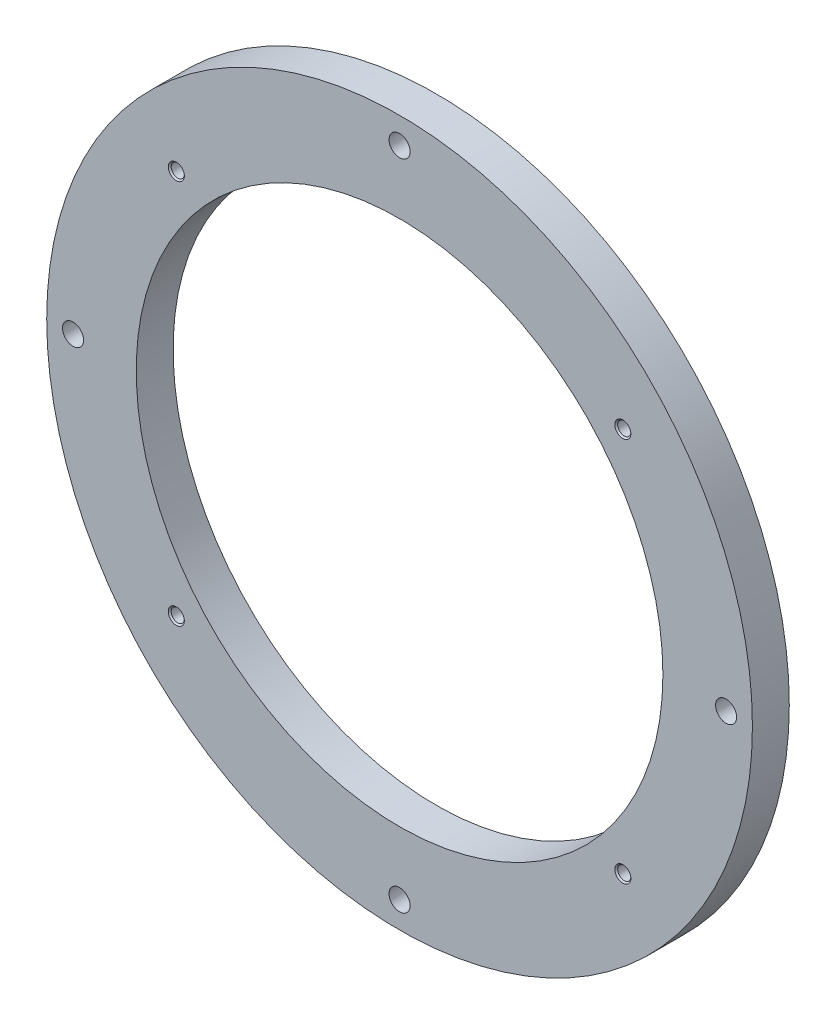
SolidWorks part; units mm, degrees
ref_plane "Piano frontale" through (0, 0, 0) normal (0, 0, 1) x (1, 0, 0)
ref_plane "Piano superiore" through (0, 0, 0) normal (0, 1, 0) x (1, 0, 0)
ref_plane "Piano destro" through (0, 0, 0) normal (1, 0, 0) x (0, 0, -1)
sketch "Schizzo2" plane through (0, 0, 0) normal (0, 0, 1) x (1, 0, 0)
  circle A0 centre (0, 0) radius 67
  point P20 (-7, -7)
  point P23 (-56.5685, -7)
  point P32 (56.5685, 7)
  point P35 (7, 56.5685)
  point P40 (-7, 7)
  point P43 (-56.5685, 7)
  point P46 (-7, 56.5685)
extrude "Estrusione-Estrusione1" add sketch "Schizzo2" along normal blind 7
sketch "Schizzo3" plane through (0, 0, 0) normal (0, 0, 1) x (1, 0, 0)
  line L0 (0, 0) -> (0, 62)
  circle A0 centre (0, 62) radius 2
extrude "Taglio-Estrusione2" cut sketch "Schizzo3" along normal up to surface (7 mm away) contours A0 up to face at (67, 0, 7)
ref_axis "Assi1" through (0, 0, 52.6425) along (0, 0, -1)
pattern_circular "RipetizioneCircolare1" count 4 every 90 about axis through (0, 0, 52.6425) along (0, 0, -1) of "Taglio-Estrusione2"
ref_plane "Piano1" through (0, 0, 7) normal (0, 0, 1) x (1, 0, 0)
sketch "Schizzo4" plane through (0, 0, 7) normal (0, 0, 1) x (1, 0, 0)
  line L0 (-42.39, -36.56) -> (-42.39, 36.56)
  line L1 (-42.39, 36.56) -> (42.39, 36.56)
  line L2 (42.39, 36.56) -> (42.39, -36.56)
  line L3 (-42.39, 36.56) -> (42.39, -36.56)
  line L4 (42.39, 36.56) -> (-42.39, -36.56)
  line L6 (-42.39, -36.56) -> (42.39, -36.56)
  circle A0 centre (0, 0) radius 60
  circle A1 centre (0, 0) radius 50
  point P6 (0, 0)
  dimension "D1" = 84.78
  dimension "D3" = 120
  dimension "D2" = 73.12
hole_wizard "Foro filettato M3-1" positions "Schizzo3D1" profile "Schizzo5" tap size "M3" standard "ISO" end condition through all
sketch3d "Schizzo3D1"
  point P0 (-42.39, -36.56, 7)
  point P3 (42.39, -36.56, 7)
  point P6 (42.39, 36.56, 7)
  point P9 (-42.39, 36.56, 7)
sketch "Schizzo5" plane through (-42.39, -36.56, 7) normal (1, 0, 0) x (0, -1, 0)
  line L0 (0, 0) -> (0, 7)
  line L1 (0, 7) -> (1.25, 7)
  line L2 (1.25, 7) -> (1.25, 0.275)
  line L3 (1.25, 0.275) -> (1.525, 0)
  line L5 (1.525, 0) -> (0, 0)
  line L6 (-1.25, 0.275) -> (-1.525, 0) construction
  line L11 (0, -6.35) -> (0, 107.95) construction
  dimension "Thru Tap Drill Dia." = 2.5
  dimension "Thru Tap Drill Depth" = 7
  dimension "Near C'Sink Dia." = 3.05
  dimension "Near C'Sink Angle" = 90
cosmetic thread "Filettatura del foro1" parameters "D1"=6, "D2"=3
cosmetic thread "Filettatura del foro2" parameters "D1"=6, "D2"=3
cosmetic thread "Filettatura del foro3" parameters "D1"=6, "D2"=3
cosmetic thread "Filettatura del foro4" parameters "D1"=6, "D2"=3
extrude "Taglio-Estrusione3" cut sketch "Schizzo4" against normal up to surface (7 mm away) contours A1 up to face at (-41.14, -36.56, 0)
